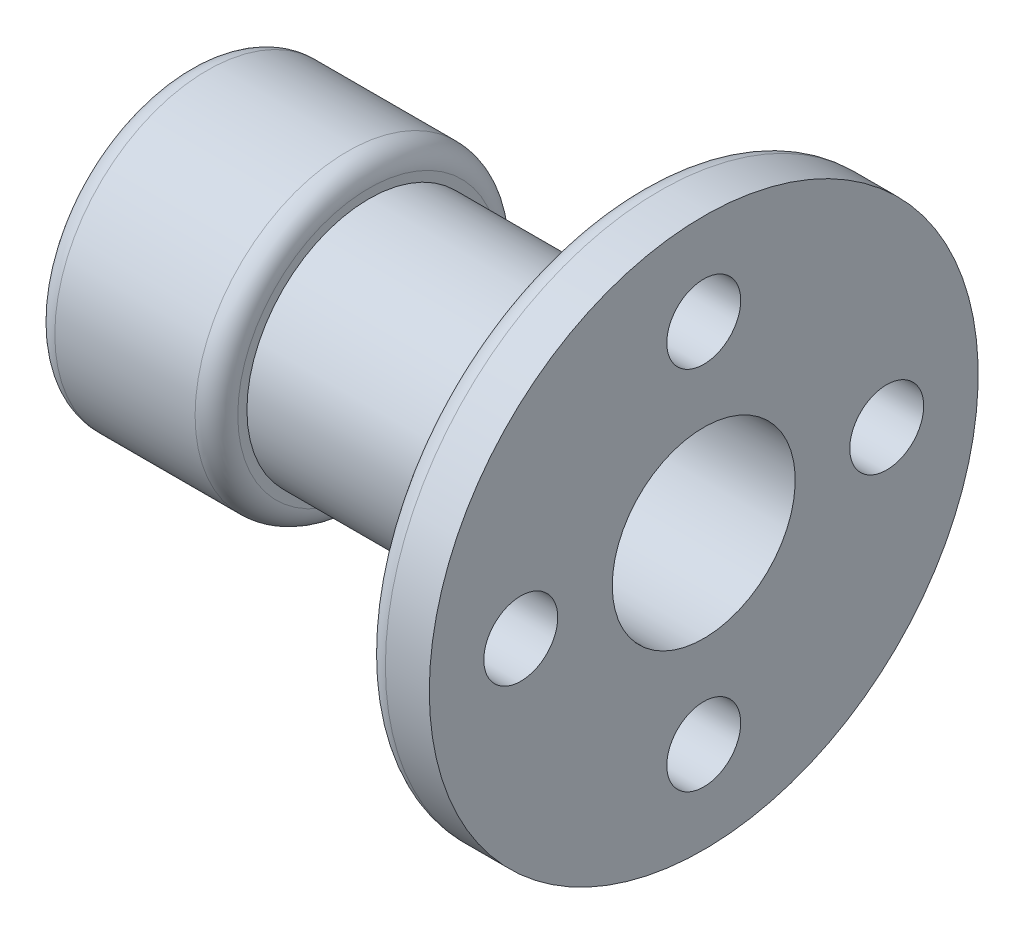
SolidWorks part; units mm, degrees
ref_plane "Front Plane" through (0, 0, 0) normal (0, 0, 1) x (1, 0, 0)
ref_plane "Top Plane" through (0, 0, 0) normal (0, 1, 0) x (1, 0, 0)
ref_plane "Right Plane" through (0, 0, 0) normal (1, 0, 0) x (0, 0, -1)
sketch "Sketch2" plane through (0, 0, 0) normal (0, 1, 0) x (1, 0, 0)
  line L0 (-50.3444, 25) -> (-20.3444, 25)
  line L1 (-20.3444, 25) -> (-20.3444, 20)
  line L2 (-20.3444, 20) -> (23.8556, 20)
  line L3 (23.8556, 20) -> (23.8556, 25)
  line L4 (23.8556, 25) -> (38.0556, 25)
  line L16 (34.5556, 15) -> (-26.3444, 15)
  line L17 (-26.3444, 15) -> (-26.3444, 19)
  line L18 (-26.3444, 19) -> (-50.3444, 19)
  line L19 (-50.3444, 19) -> (-50.3444, 25)
  line L20 (23.8556, 25) -> (23.8556, 45)
  line L21 (23.8556, 45) -> (38.0556, 45)
  line L22 (38.0556, 45) -> (38.0556, 25)
  line L23 (23.8556, 37.5) -> (38.0556, 37.5)
  line L24 (34.5556, 15) -> (34.5556, 0)
  line L25 (38.0556, 25) -> (38.0556, -25)
  line L26 (-47.3611, 0) -> (63.75, 0) construction
  line L27 (-26.3444, -37.5) -> (-26.3444, 57.57)
  line L28 (23.8556, -37.5) -> (38.0556, -37.5)
  line L29 (38.0556, -45) -> (38.0556, -25)
  line L30 (23.8556, -45) -> (38.0556, -45)
  line L31 (23.8556, -25) -> (23.8556, -45)
  line L32 (34.5556, -15) -> (34.5556, 0)
  line L33 (-50.3444, -19) -> (-50.3444, -25)
  line L34 (-26.3444, -19) -> (-50.3444, -19)
  line L35 (-26.3444, -15) -> (-26.3444, -19)
  line L36 (34.5556, -15) -> (-26.3444, -15)
  line L37 (23.8556, -25) -> (38.0556, -25)
  line L38 (23.8556, -20) -> (23.8556, -25)
  line L39 (-20.3444, -20) -> (23.8556, -20)
  line L40 (-20.3444, -25) -> (-20.3444, -20)
  line L41 (-50.3444, -25) -> (-20.3444, -25)
  line L42 (-20.3444, -34.2268) -> (-20.3444, 57.57)
  line L43 (23.8556, -66.4229) -> (23.8556, 72.846)
  line L44 (34.5556, -68.4122) -> (34.5556, 61.2225)
  line L45 (38.0556, -56.193) -> (38.0556, 67.625)
  point P13 (38.0556, 0)
  dimension "D1" = 25
  dimension "D2" = 30
  dimension "D3" = 24
  dimension "D4" = 44.2
  dimension "D5" = 14.2
  dimension "D6" = 15
  dimension "D7" = 5
  dimension "D8" = 3.5
  dimension "D9" = 19
  dimension "D10" = 25
  dimension "D11" = 45
  dimension "D12" = 12.5
  dimension "D13" = 7.5
  dimension "D14" = 15
revolve "Revolve5" add sketch "Sketch2" angle 360 about L26 region at (-38.3444, 0, -22) region at (-23.3444, 0, -20) region at (1.7556, 0, -17.5) region at (29.2056, 0, -20) region at (-23.3444, 0, 20) region at (1.7556, 0, 17.5) region at (-38.3444, 0, 22) region at (29.2056, 0, -41.25) region at (29.2056, 0, 20) region at (29.2056, 0, 31.25) region at (29.2056, 0, 41.25)
sketch "Sketch5" plane through (34.5556, 0, 0) normal (1, 0, 0) x (0, 0, -1)
  circle A0 centre (0, 30) radius 6.0612
  circle A3 centre (30, 0) radius 6.0612
  circle A4 centre (0, -30) radius 6.0612
  circle A5 centre (-30, 0) radius 6.0612
  point P14 (0, 0)
  dimension "D1" = 4
extrude "Cut-Extrude2" cut sketch "Sketch5" against normal up to next
fillet "Fillet2" radius 3.5 1 edges at (-20.3444, 0, 25)
fillet "Fillet3" radius 3.5 3 edges at (23.8556, 0, 45) (23.8556, 0, 20) (-50.3444, 0, 25)
